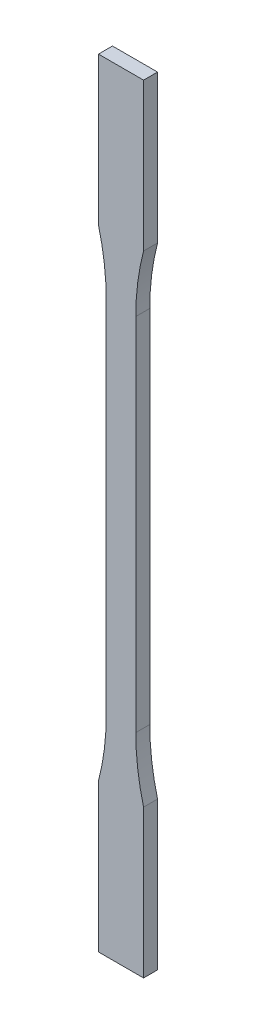
SolidWorks part; units mm, degrees
material "ABS"
ref_plane "Front Plane" through (0, 0, 0) normal (0, 0, 1) x (1, 0, 0)
ref_plane "Top Plane" through (0, 0, 0) normal (0, 1, 0) x (1, 0, 0)
ref_plane "Right Plane" through (0, 0, 0) normal (1, 0, 0) x (0, 0, -1)
sketch "Sketch1" plane through (0, 0, 0) normal (0, 0, 1) x (1, 0, 0)
  line L1 (-14.5, -250) -> (14.5, -250)
  line L2 (-14.5, -250) -> (-14.5, 250)
  line L3 (-14.5, 250) -> (14.5, 250)
  line L4 (14.5, -250) -> (14.5, 250)
  line L5 (-14.5, -250) -> (14.5, 250) construction
  line L6 (-14.5, 250) -> (14.5, -250) construction
  point P0 (0, 0)
  dimension "D1" = 500
  dimension "D2" = 29
extrude "Boss-Extrude1" add sketch "Sketch1" along normal mid plane 9
sketch "Sketch2" plane through (0, 0, 4.5) normal (0, 0, 1) x (1, 0, 0)
  line L0 (-14.5, 0) -> (14.5, 0) construction
  line L1 (14.5, -250) -> (14.5, 250) construction
  line L2 (14.5, -76.8701) -> (14.5, 76.8701)
  line L3 (-14.5, -76.8701) -> (-14.5, 76.8701)
  line L4 (0, 250) -> (0, -250) construction
  line L5 (-14.5, -250) -> (14.5, -250) construction
  line L6 (9.5, 115.8537) -> (9.5, -115.8537)
  line L7 (-9.5, 115.8537) -> (-9.5, -115.8537)
  circle A0 centre (163.9715, 115.8537) radius 154.4715
  circle A1 centre (-163.9715, 115.8537) radius 154.4715
  circle A2 centre (-163.9715, -115.8537) radius 154.4715
  circle A3 centre (163.9715, -115.8537) radius 154.4715
  point P5 (0, 0)
  point P11 (0, 0)
  point P23 (-9.5, 0)
  point P27 (9.5, 0)
  line M1 (14.5, -250) -> (14.5, 250)
  line M3 (-14.5, 250) -> (-14.5, -250)
  dimension "D3" = 154.4715
  dimension "D1" = 9.5
  dimension "D2" = 115.8537
extrude "Cut-Extrude1" cut sketch "Sketch2" against normal through all both and the other way through all contours A2 L7 A1 M3 | L6 A3 A0 M1 | A3 M1 | A2 M3 | A1 M3 | A0 M1 region at (11.8556, 0, 4.5) region at (12.4972, -115.8537, 4.5) region at (12.4972, 115.8537, 4.5) region at (-11.8556, 0, 4.5) region at (-12.4972, -115.8537, 4.5) region at (-12.4972, 115.8537, 4.5)
equation "\"WO\"= 29mm'Overall Width"
equation "\"LO\"= 246mm * \"LM\"'Overall Length"
equation "\"T\"= 9mm'Thickness"
equation "\"W\"= 19mm'Width of Narrow Section"
equation "\"L\"= 57mm * \"LM\"'Length of Narrow Section"
equation "\"G\"= 50mm * \"LM\"'Gage Length"
equation "\"R\"= 76mm * \"LM\"'Fillet Radius"
equation "\"D\"= 115mm * \"LM\"'Distance between Grips"
equation "\"D1@Sketch1\"=\"LO\""
equation "\"D2@Sketch1\"=\"WO\""
equation "\"D1@Boss-Extrude1\"=\"T\""
equation "\"GL\"= ( ( \"LO\" - \"D\" ) / 2 ) + 5mm'Length of Grip Section"
equation "\"LM\"= 500 / 246'Length Multiplier"
equation "\"D1@Sketch2\"=\"W\"/2"
equation "\"D2@Sketch2\"=\"L\""
equation "\"D3@Sketch2\"=\"R\""
